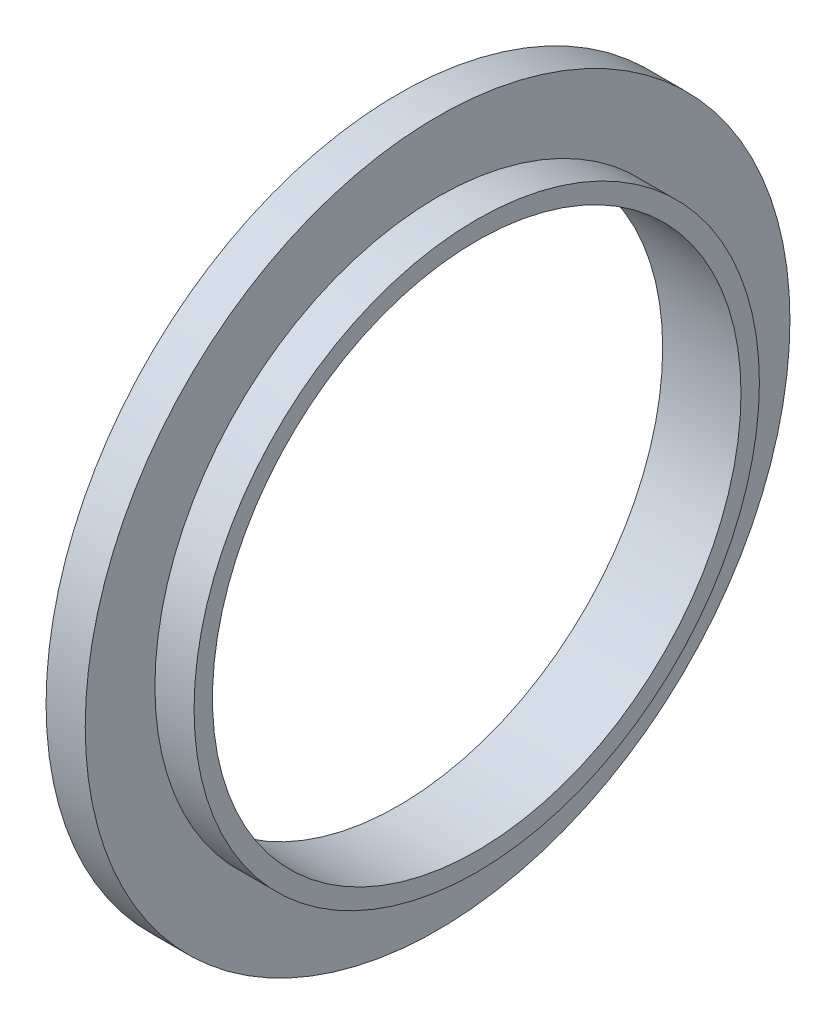
SolidWorks part; units mm, degrees
material "7075-T6 (SN)"
ref_plane "Front Plane" through (0, 0, 0) normal (0, 0, 1) x (1, 0, 0)
ref_plane "Top Plane" through (0, 0, 0) normal (0, 1, 0) x (1, 0, 0)
ref_plane "Right Plane" through (0, 0, 0) normal (1, 0, 0) x (0, 0, -1)
sketch "Sketch1" plane through (0, 0, 0) normal (1, 0, 0) x (0, 0, -1)
  circle A0 centre (0, 0) radius 42.8625
  circle A1 centre (0, 0) radius 57.15
  dimension "D1" = 85.725
  dimension "D2" = 114.3
extrude "Boss-Extrude1" add sketch "Sketch1" along normal blind 6.35
sketch "Sketch2" plane through (6.35, 0, 0) normal (1, 0, 0) x (0, 0, -1)
  circle A0 centre (0, 0) radius 45.847
  circle A1 centre (0, 0) radius 42.8625
  dimension "D1" = 91.694
  dimension "D2" = 85.725
extrude "Boss-Extrude2" add sketch "Sketch2" along normal blind 6.35
